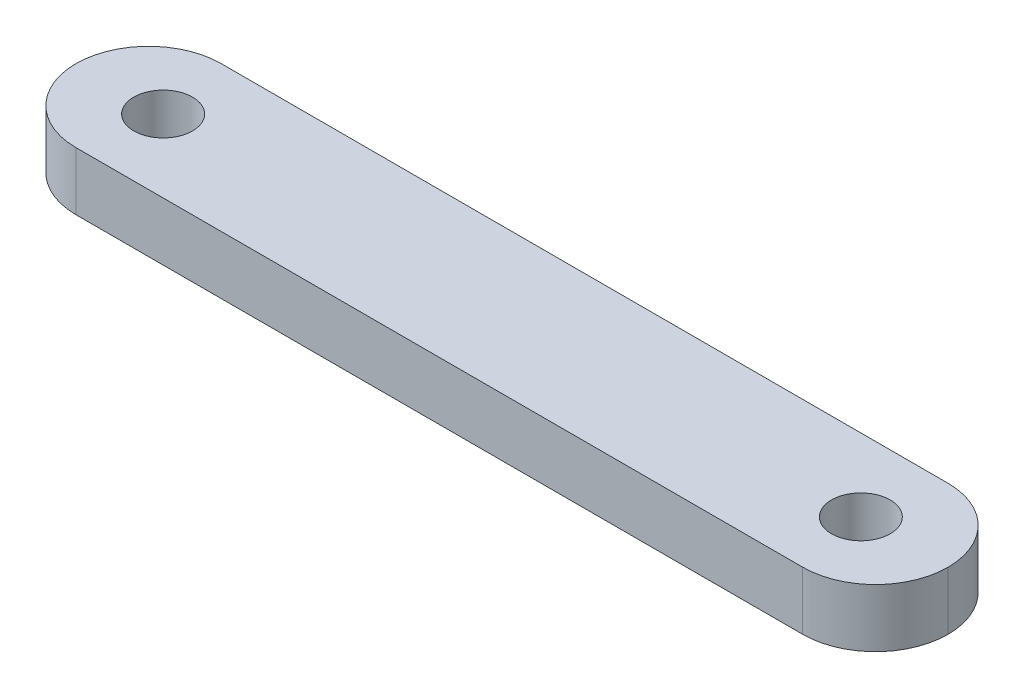
SolidWorks part; units mm, degrees
ref_plane "Спереди" through (0, 0, 0) normal (0, 0, 1) x (1, 0, 0)
ref_plane "Сверху" through (0, 0, 0) normal (0, 1, 0) x (1, 0, 0)
ref_plane "Справа" through (0, 0, 0) normal (1, 0, 0) x (0, 0, -1)
sketch "Эскиз1" plane through (0, 0, 0) normal (0, 1, 0) x (1, 0, 0)
  line L0 (0, 12.5) -> (0, 0) construction
  line L1 (-75, 12.5) -> (75, 12.5)
  line L2 (-75, 12.5) -> (-75, -12.5)
  line L3 (-75, -12.5) -> (75, -12.5)
  line L4 (75, 12.5) -> (75, -12.5)
  line L5 (0, 0) -> (75, 0) construction
  dimension "D1" = 150
  dimension "D2" = 25
extrude "Бобышка-Вытянуть2" add sketch "Эскиз1" along normal blind 10
sketch "Эскиз5" plane through (0, 10, 0) normal (0, 1, 0) x (1, 0, 0)
  line L0 (-60, 0) -> (60, 0) construction
  line L1 (0, 12.5) -> (0, 0) construction
  line L2 (75, 12.5) -> (-75, 12.5) construction
  circle A0 centre (-60, 0) radius 5.05
  dimension "D2" = 10.1
  dimension "D1" = 120
extrude "Вырез-Вытянуть4" cut sketch "Эскиз5" against normal through all
mirror "Зеркальное отражение1" about plane through (0, 0, 0) normal (1, 0, 0) of "Вырез-Вытянуть4"
fillet "Скругление1" radius 12.5 4 edges at (-75, 5, 12.5) (-75, 5, -12.5) (75, 5, 12.5) (75, 5, -12.5)
